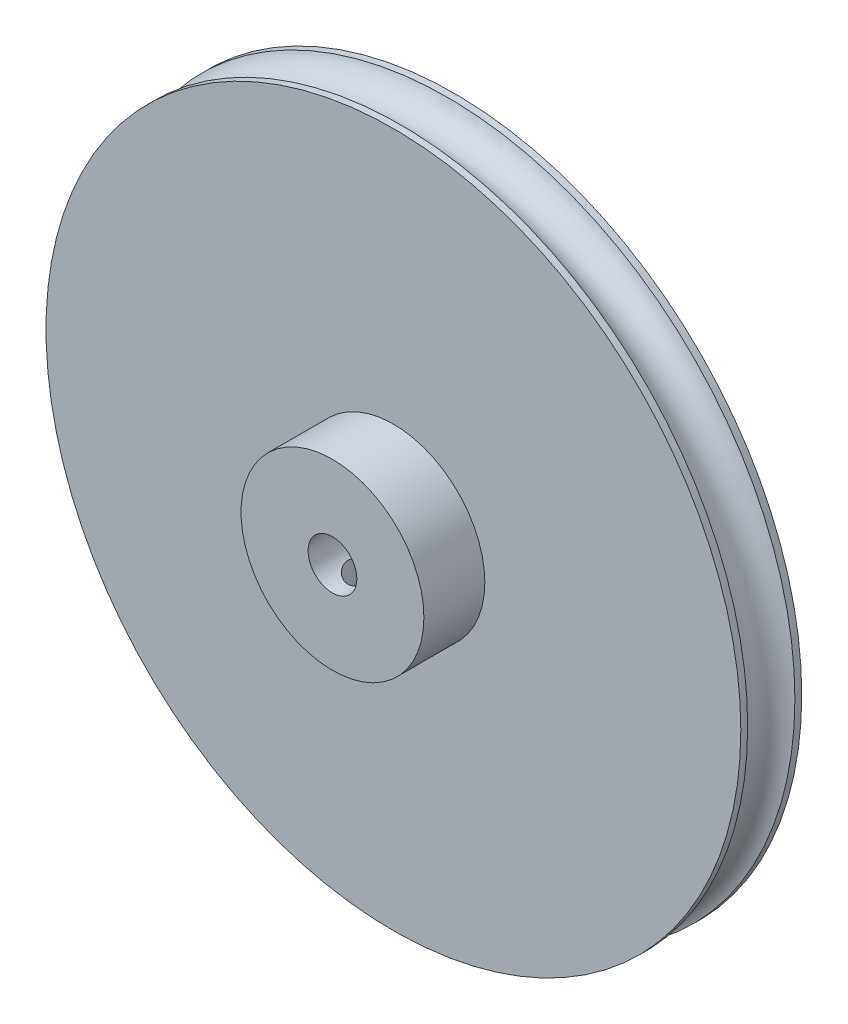
SolidWorks part; units mm, degrees
ref_plane "Plan de face" through (0, 0, 0) normal (0, 0, 1) x (1, 0, 0)
ref_plane "Plan de dessus" through (0, 0, 0) normal (0, 1, 0) x (1, 0, 0)
ref_plane "Plan de droite" through (0, 0, 0) normal (1, 0, 0) x (0, 0, -1)
sketch "Esquisse1" plane through (0, 0, 0) normal (0, 0, 1) x (1, 0, 0)
  circle A0 centre (0, 0) radius 28.5
  dimension "D1" = 57
extrude "Extrusion1" add sketch "Esquisse1" against normal blind 5
sketch "Esquisse2" plane through (0, 0, 0) normal (0, 0, 1) x (1, 0, 0)
  circle A0 centre (0, 0) radius 7.5
  dimension "D1" = 15
extrude "Extrusion2" add sketch "Esquisse2" along normal blind 5
sketch "Esquisse3" plane through (0, 0, 5) normal (0, 0, 1) x (1, 0, 0)
  circle A0 centre (0, 0) radius 2
  dimension "D1" = 4
extrude "Extrusion3" cut sketch "Esquisse3" against normal up to next
sketch "Esquisse6" plane through (0, 0, 0) normal (0, 1, 0) x (1, 0, 0)
  line L0 (-29, 2.5) -> (-27, 2.5) construction
  line L1 (-29, 4.5) -> (-31.4496, 4.5)
  line L2 (-29, 0.5) -> (-31.4496, 0.5)
  line L3 (-28.5, 0) -> (28.5, 0) construction
  line L4 (-29, 0) -> (-29, 0.5) construction
  line L5 (-29, 5) -> (-29, 4.5) construction
  line L6 (28.5, 5) -> (-28.5, 5) construction
  line L7 (-31.4496, 0.5) -> (-31.4496, 4.5)
  line L8 (-29, 0.5) -> (-29, 2.5) construction
  arc A0 (-29, 0.5) -> (-29, 4.5) centre (-29, 2.5) ccw
  dimension "D1" = 2
  dimension "D2" = 0.5
  dimension "D3" = 27
revolve "Enlèvement de matière-Révolution3" cut sketch "Esquisse6" angle 360 about axis through (0, 0, 5) along (0, 0, -1)
ref_plane "Plan1" through (0, 0, 0) normal (0, 1, 0) x (1, 0, 0)
sketch "Esquisse11" plane through (0, 0, 0) normal (0, 1, 0) x (1, 0, 0)
  line L0 (0, 0) -> (0, -5) construction
  line L1 (-7.5, -5) -> (7.5, -5) construction
  point P5 (0, -2.5)
hole_wizard "Trou taraudé M3x0.55" positions "Esquisse13" profile "Esquisse12" tap size "M3x0.5" standard "Ansi Metric" end condition through all
sketch "Esquisse13" plane through (0, 0, 0) normal (0, 1, 0) x (1, 0, 0)
  line L0 (0, 0) -> (0, -5) construction
  point P8 (0, -2.5)
sketch "Esquisse12" plane through (0, 0, 2.5) normal (1, 0, 0) x (0, 0, 1)
  line L0 (0, 0) -> (0, 28.5)
  line L1 (0, 28.5) -> (1.25, 28.5)
  line L2 (1.25, 28.5) -> (1.25, 0)
  line L5 (1.25, 0) -> (0, 0)
  line L11 (0, -6.35) -> (0, 107.95) construction
  dimension "Diamètre du trou pour taraudage jusqu'au prochain" = 2.5
  dimension "Profondeur du trou pour taraudage jusqu'au prochain" = 28.5
cosmetic thread "Filetage de perçage1" parameters "D2"=3
